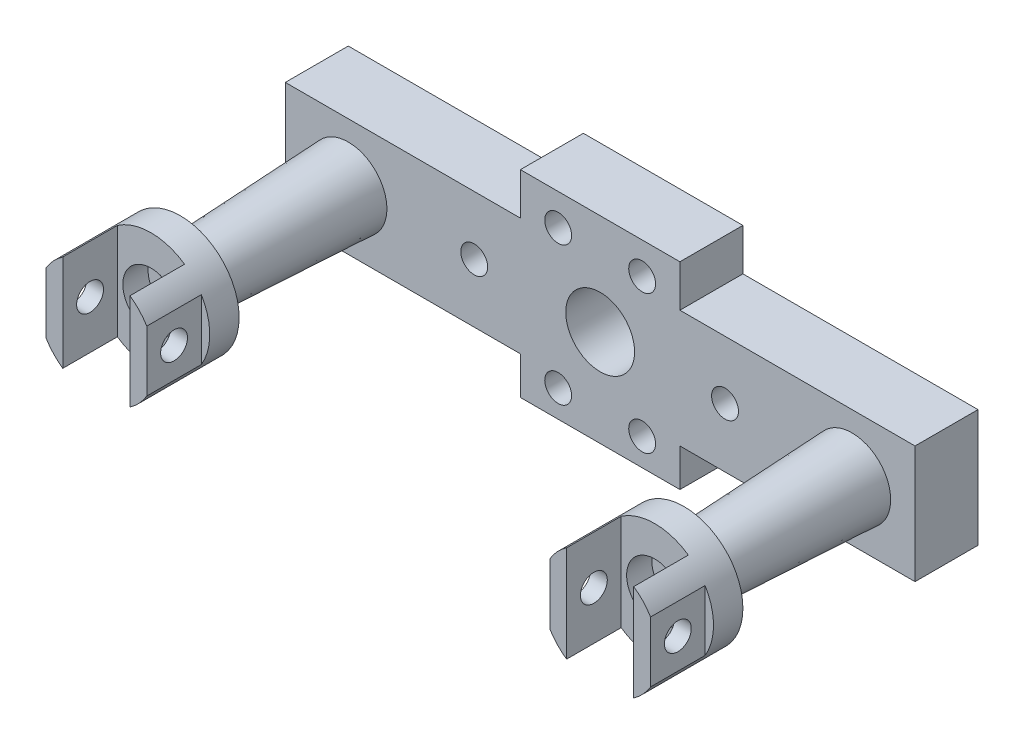
SolidWorks part; units mm, degrees
ref_plane "前视基准面" through (0, 0, 0) normal (0, 0, 1) x (1, 0, 0)
ref_plane "上视基准面" through (0, 0, 0) normal (0, 1, 0) x (1, 0, 0)
ref_plane "右视基准面" through (0, 0, 0) normal (1, 0, 0) x (0, 0, -1)
sketch "草图1" plane through (0, 0, 0) normal (0, 0, 1) x (1, 0, 0)
  line L0 (0, 11.5) -> (9.1, 11.5) construction
  line L1 (37.5, 34.267) -> (37.5, 15.6) construction
  line L2 (0, 11.5) -> (0, 4.5)
  line L3 (65.9, 11.5) -> (75, 11.5) construction
  line L4 (75, 4.5) -> (75, 18.5)
  line L5 (75, 11.5) -> (69.1, 11.5) construction
  line L6 (75, 18.5) -> (47, 18.5)
  line L7 (47, 18.5) -> (47, 23.5)
  line L8 (47, 23.5) -> (28, 23.5)
  line L9 (28, 23.5) -> (28, 18.5)
  line L10 (28, 18.5) -> (0, 18.5)
  line L11 (5.9, 11.5) -> (0, 11.5) construction
  line L12 (0, 18.5) -> (0, 11.5)
  line L13 (28, 0) -> (47, 0)
  line L15 (20.1, 11.5) -> (20.9, 11.5) construction
  line L16 (75, 4.5) -> (47, 4.5)
  line L17 (47, 4.5) -> (47, 0)
  line L18 (37.5, 7.4) -> (37.5, 0) construction
  line L19 (28, 4.5) -> (28, 0)
  line L20 (28, 4.5) -> (0.4162, 4.5)
  line L21 (0.4162, 4.5) -> (0, 4.5)
  circle A0 centre (37.5, 11.5) radius 4.1
  circle A5 centre (67.5, 11.5) radius 1.6
  circle A6 centre (32.5, 3.2278) radius 1.6
  circle A7 centre (42.5, 3.25) radius 1.6
  circle A8 centre (42.5, 19.75) radius 1.6
  circle A9 centre (32.5, 19.75) radius 1.6
  circle A10 centre (7.5, 11.5) radius 1.6
  circle A11 centre (52.3705, 11.554) radius 1.6
  circle A12 centre (22.5, 11.5) radius 1.6
extrude "凸台-拉伸1" add sketch "草图1" along normal blind 7.5
sketch "草图2" plane through (0, 0, 0) normal (0, 0, -1) x (-1, 0, 0)
  line L1 (-38.8627, 19.75) -> (-40.6813, 22.9)
  line L2 (-40.6813, 22.9) -> (-44.3187, 22.9)
  line L3 (-44.3187, 22.9) -> (-46.1373, 19.75)
  line L4 (-46.1373, 19.75) -> (-44.3187, 16.6)
  line L5 (-44.3187, 16.6) -> (-40.6813, 16.6)
  line L6 (-40.6813, 16.6) -> (-38.8627, 19.75)
  line L7 (-28.8627, 19.75) -> (-30.6814, 22.9)
  line L8 (-30.6814, 22.9) -> (-34.3187, 22.9)
  line L9 (-34.3187, 22.9) -> (-36.1373, 19.75)
  line L10 (-36.1373, 19.75) -> (-34.3187, 16.6)
  line L11 (-34.3187, 16.6) -> (-30.6814, 16.6)
  line L12 (-30.6814, 16.6) -> (-28.8627, 19.75)
  line L13 (-38.8627, 3.25) -> (-40.6813, 6.4)
  line L14 (-40.6813, 6.4) -> (-44.3187, 6.4)
  line L15 (-44.3187, 6.4) -> (-46.1373, 3.25)
  line L16 (-46.1373, 3.25) -> (-44.3187, 0.1)
  line L17 (-44.3187, 0.1) -> (-40.6813, 0.1)
  line L18 (-40.6813, 0.1) -> (-38.8627, 3.25)
  line L19 (-28.8627, 3.2278) -> (-30.6814, 6.3778)
  line L20 (-30.6814, 6.3778) -> (-34.3187, 6.3778)
  line L21 (-34.3187, 6.3778) -> (-36.1373, 3.2278)
  line L22 (-36.1373, 3.2278) -> (-34.3187, 0.0778)
  line L23 (-34.3187, 0.0778) -> (-30.6814, 0.0778)
  line L24 (-30.6814, 0.0778) -> (-28.8627, 3.2278)
  line L25 (-63.8627, 11.5) -> (-65.6813, 14.65)
  line L26 (-65.6813, 14.65) -> (-69.3187, 14.65)
  line L27 (-69.3187, 14.65) -> (-71.1373, 11.5)
  line L28 (-71.1373, 11.5) -> (-69.3187, 8.35)
  line L29 (-69.3187, 8.35) -> (-65.6813, 8.35)
  line L30 (-65.6813, 8.35) -> (-63.8627, 11.5)
  line L31 (-3.8627, 11.5) -> (-5.6813, 14.65)
  line L32 (-5.6813, 14.65) -> (-9.3187, 14.65)
  line L33 (-9.3187, 14.65) -> (-11.1373, 11.5)
  line L34 (-11.1373, 11.5) -> (-9.3187, 8.35)
  line L35 (-9.3187, 8.35) -> (-5.6813, 8.35)
  line L36 (-5.6813, 8.35) -> (-3.8627, 11.5)
  circle A0 centre (-42.5, 19.75) radius 3.15 construction
  circle A1 centre (-32.5, 19.75) radius 3.15 construction
  circle A2 centre (-42.5, 3.25) radius 3.15 construction
  circle A3 centre (-32.5, 3.2278) radius 3.15 construction
  circle A4 centre (-67.5, 11.5) radius 3.15 construction
  circle A5 centre (-7.5, 11.5) radius 3.15 construction
extrude "切除-拉伸1" cut sketch "草图2" against normal blind 2.5
sketch "草图4" plane through (0, 0, 7.5) normal (0, 0, 1) x (1, 0, 0)
  circle A0 centre (7.5, 11.5) radius 1.6
  circle A1 centre (7.5, 11.5) radius 3.6
  circle A2 centre (67.5, 11.5) radius 3.6
  circle A3 centre (67.5, 11.5) radius 1.6
extrude "凸台-拉伸2" add sketch "草图4" along normal blind 20
sketch "草图5" plane through (0, 0, 27.5) normal (0, 0, 1) x (1, 0, 0)
  circle A0 centre (7.5, 11.5) radius 7
  circle A1 centre (67.5, 11.5) radius 7
  circle A2 centre (7.5, 11.5) radius 1.6
  circle A3 centre (67.5, 11.5) radius 1.6
extrude "凸台-拉伸3" add sketch "草图5" along normal blind 10
sketch "草图6" plane through (0, 0, 37.5) normal (0, 0, 1) x (1, 0, 0)
  line L1 (1.5, 7.8944) -> (1.5, 15.1056)
  line L2 (73.5, 15.1056) -> (73.5, 7.8944)
  line L3 (3.5, 5.7554) -> (3.5, 17.2446)
  line L4 (71.5, 7.8944) -> (71.5, 17.2446)
  line L5 (71.5, 7.8944) -> (71.5, 5.7554)
  line L6 (11.5, 5.7554) -> (11.5, 17.2446)
  line L7 (13.5, 15.1056) -> (13.5, 7.8944)
  line L8 (61.5, 7.8944) -> (61.5, 15.1056)
  line L9 (63.5, 17.2446) -> (63.5, 5.7554)
  circle A0 centre (7.5, 11.5) radius 7 construction
  circle A1 centre (67.5, 11.5) radius 7 construction
  arc A2 (73.5, 7.8944) -> (73.5, 15.1056) centre (67.5, 11.5) ccw
  arc A3 (13.5, 7.8944) -> (13.5, 15.1056) centre (7.5, 11.5) ccw
  arc A4 (11.5, 17.2446) -> (3.5, 17.2446) centre (7.5, 11.5) ccw
  arc A5 (1.5, 15.1056) -> (1.5, 7.8944) centre (7.5, 11.5) ccw
  arc A6 (3.5, 5.7554) -> (11.5, 5.7554) centre (7.5, 11.5) ccw
  arc A7 (71.5, 17.2446) -> (63.5, 17.2446) centre (67.5, 11.5) ccw
  arc A8 (61.5, 15.1056) -> (61.5, 7.8944) centre (67.5, 11.5) ccw
  arc A9 (63.5, 5.7554) -> (71.5, 5.7554) centre (67.5, 11.5) ccw
extrude "切除-拉伸2" cut sketch "草图6" against normal blind 6.5
sketch "草图7" plane through (1.5, 0, 0) normal (-1, 0, 0) x (0, 0, 1)
  line L0 (34.25, 15.1056) -> (34.25, 7.8944) construction
  line L1 (31, 15.1056) -> (37.5, 15.1056) construction
  line L2 (31, 7.8944) -> (37.5, 7.8944) construction
  circle A0 centre (34.25, 11.5) radius 1.6
extrude "切除-拉伸3" cut sketch "草图7" against normal through all
chamfer "倒角1" distance 1 distance2 22 2 edges at (63.9, 11.5, 7.5) (3.9, 11.5, 7.5) first distance on face at (3.9, 11.5, 7.5)
sketch "草图9" plane through (0, 0, 31) normal (0, 0, 1) x (1, 0, 0)
  circle A0 centre (7.5, 11.5) radius 3.35
extrude "切除-拉伸4" cut sketch "草图9" against normal blind 3
sketch "草图11" plane through (0, 0, 31) normal (0, 0, 1) x (1, 0, 0)
  circle A0 centre (67.5, 11.5) radius 3.35
extrude "切除-拉伸5" cut sketch "草图11" against normal blind 3
